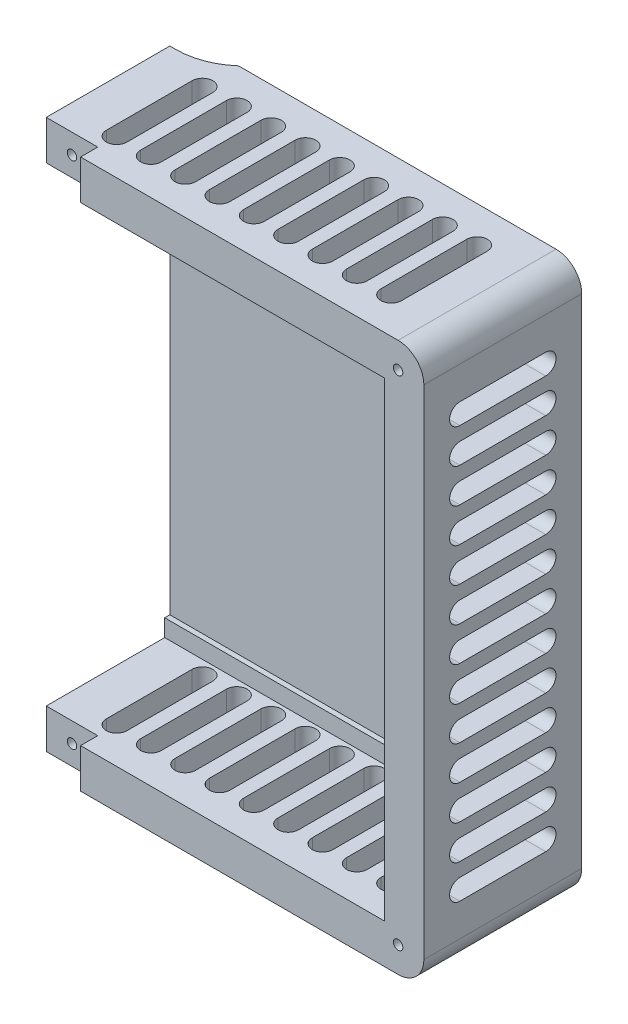
SolidWorks part; units mm, degrees
ref_plane "Front Plane" through (0, 0, 0) normal (0, 0, 1) x (1, 0, 0)
ref_plane "Top Plane" through (0, 0, 0) normal (0, 1, 0) x (1, 0, 0)
ref_plane "Right Plane" through (0, 0, 0) normal (1, 0, 0) x (0, 0, -1)
sketch "Sketch1" plane through (0, 0, 0) normal (0, 0, 1) x (1, 0, 0)
  line L1 (-115, 80) -> (115, 80)
  line L2 (-115, 80) -> (-115, -80)
  line L3 (-115, -80) -> (115, -80)
  line L4 (115, 80) -> (115, -80)
  line L5 (-115, 80) -> (115, -80) construction
  line L6 (-115, -80) -> (115, 80) construction
  point P0 (0, 0)
  dimension "D1" = 230
  dimension "D2" = 160
extrude "Boss-Extrude1" add sketch "Sketch1" along normal blind 46
shell "Shell1" thickness 11.5 removed face at (0, 0, 46)
sketch "Sketch3" plane through (0, 0, 46) normal (0, 0, 1) x (1, 0, 0)
  line L1 (-115, -80) -> (115, -80) construction
  line L2 (0, 80) -> (-115, 80)
  line L3 (0, 80) -> (0, -80)
  line L4 (0, -80) -> (-115, -80)
  line L5 (-115, 80) -> (-115, -80)
  line L7 (-115, 80) -> (-115, -80) construction
  dimension "D1" = 115
extrude "Cut-Extrude3" cut sketch "Sketch3" against normal up to surface (46 mm away) up to face at (0, 0, 0)
ref_plane "Plane1" through (0, 0, 23) normal (0, 0, 1) x (1, 0, 0)
sketch "Sketch12" plane through (0, 0, 11.5) normal (0, 0, 1) x (1, 0, 0)
  line L0 (103.5, 68.5) -> (0, 68.5) construction
  line L1 (103.5, 68.5) -> (0, 68.5)
  line L2 (103.5, 68.5) -> (103.5, -68.5)
  line L3 (103.5, -68.5) -> (0, -68.5)
  line L4 (0, 68.5) -> (0, -68.5)
  line L5 (103.5, 68.5) -> (0, -68.5) construction
  line L6 (103.5, -68.5) -> (0, 68.5) construction
  line L7 (103.5, -68.5) -> (103.5, 68.5) construction
  line L8 (0, -68.5) -> (103.5, -68.5) construction
  line L9 (0, -68.5) -> (0, 68.5) construction
  point P0 (51.75, 0)
extrude "Cut-Extrude11" cut sketch "Sketch12" against normal blind 5
sketch "Sketch13" plane through (0, 0, 6.5) normal (0, 0, 1) x (1, 0, 0)
  line L0 (103.5, -68.5) -> (103.5, 68.5) construction
  line L1 (91, 63.5) -> (0, 63.5)
  line L2 (98.5, 56) -> (98.5, -56)
  line L3 (91, -63.5) -> (0, -63.5)
  line L4 (0, 63.5) -> (0, -63.5)
  line L5 (98.5, 63.5) -> (0, -63.5) construction
  line L6 (98.5, -63.5) -> (0, 63.5) construction
  line L7 (103.5, 68.5) -> (0, 68.5) construction
  line L9 (0, -68.5) -> (103.5, -68.5) construction
  arc A0 (98.5, -56) -> (91, -63.5) centre (91, -56) cw
  arc A1 (91, 63.5) -> (98.5, 56) centre (91, 56) cw
  point P0 (49.25, 0)
  dimension "D3" = 7.5
  dimension "D1" = 5
  dimension "D2" = 5
  dimension "D4" = 5
extrude "Cut-Extrude12" cut sketch "Sketch13" against normal blind 1.5
sketch "Sketch14" plane through (0, 80, 0) normal (0, 1, 0) x (1, 0, 0)
  line L0 (98, -35.5) -> (98, -10.5)
  line L1 (92, -35.5) -> (92, -10.5)
  line L3 (115, -46) -> (115, 0) construction
  line L4 (115, -46) -> (0, -46) construction
  line L6 (88, -35.5) -> (88, -10.5)
  line L7 (82, -35.5) -> (82, -10.5)
  line L8 (78, -35.5) -> (78, -10.5)
  line L9 (72, -35.5) -> (72, -10.5)
  line L10 (68, -35.5) -> (68, -10.5)
  line L11 (62, -35.5) -> (62, -10.5)
  line L12 (58, -35.5) -> (58, -10.5)
  line L13 (52, -35.5) -> (52, -10.5)
  line L14 (48, -35.5) -> (48, -10.5)
  line L15 (42, -35.5) -> (42, -10.5)
  line L16 (38, -35.5) -> (38, -10.5)
  line L17 (32, -35.5) -> (32, -10.5)
  line L18 (28, -35.5) -> (28, -10.5)
  line L19 (22, -35.5) -> (22, -10.5)
  line L20 (18, -35.5) -> (18, -10.5)
  line L21 (12, -35.5) -> (12, -10.5)
  arc A0 (98, -35.5) -> (92, -35.5) centre (95, -35.5) cw
  arc A1 (92, -10.5) -> (98, -10.5) centre (95, -10.5) cw
  arc A2 (88, -35.5) -> (82, -35.5) centre (85, -35.5) cw
  arc A3 (82, -10.5) -> (88, -10.5) centre (85, -10.5) cw
  arc A4 (78, -35.5) -> (72, -35.5) centre (75, -35.5) cw
  arc A5 (72, -10.5) -> (78, -10.5) centre (75, -10.5) cw
  arc A6 (68, -35.5) -> (62, -35.5) centre (65, -35.5) cw
  arc A7 (62, -10.5) -> (68, -10.5) centre (65, -10.5) cw
  arc A8 (58, -35.5) -> (52, -35.5) centre (55, -35.5) cw
  arc A9 (52, -10.5) -> (58, -10.5) centre (55, -10.5) cw
  arc A10 (48, -35.5) -> (42, -35.5) centre (45, -35.5) cw
  arc A11 (42, -10.5) -> (48, -10.5) centre (45, -10.5) cw
  arc A12 (38, -35.5) -> (32, -35.5) centre (35, -35.5) cw
  arc A13 (32, -10.5) -> (38, -10.5) centre (35, -10.5) cw
  arc A14 (28, -35.5) -> (22, -35.5) centre (25, -35.5) cw
  arc A15 (22, -10.5) -> (28, -10.5) centre (25, -10.5) cw
  arc A16 (18, -35.5) -> (12, -35.5) centre (15, -35.5) cw
  arc A17 (12, -10.5) -> (18, -10.5) centre (15, -10.5) cw
  point P8 (95, -38.5)
  dimension "D2" = 3
  dimension "D3" = 17
  dimension "D1" = 25
  dimension "D4" = 7.5
  dimension "D5" = 9
extrude "Cut-Extrude13" cut sketch "Sketch14" against normal blind 12
mirror "Mirror9" about plane through (0, 0, 0) normal (0, 1, 0) of "Cut-Extrude13"
sketch "Sketch15" plane through (115, 0, 0) normal (1, 0, 0) x (0, 0, -1)
  line L0 (-35.5, -63) -> (-10.5, -63)
  line L1 (-10.5, -57) -> (-35.5, -57)
  line L2 (-46, -80) -> (0, -80) construction
  line L3 (-46, -80) -> (-46, 80) construction
  line L9 (-35.5, -53) -> (-10.5, -53)
  line L10 (-10.5, -47) -> (-35.5, -47)
  line L11 (-35.5, -43) -> (-10.5, -43)
  line L12 (-10.5, -37) -> (-35.5, -37)
  line L13 (-35.5, -33) -> (-10.5, -33)
  line L14 (-10.5, -27) -> (-35.5, -27)
  line L15 (-35.5, -23) -> (-10.5, -23)
  line L16 (-10.5, -17) -> (-35.5, -17)
  line L17 (-35.5, -13) -> (-10.5, -13)
  line L18 (-10.5, -7) -> (-35.5, -7)
  line L19 (-35.5, -3) -> (-10.5, -3)
  line L20 (-10.5, 3) -> (-35.5, 3)
  line L21 (-35.5, 7) -> (-10.5, 7)
  line L22 (-10.5, 13) -> (-35.5, 13)
  line L23 (-35.5, 17) -> (-10.5, 17)
  line L24 (-10.5, 23) -> (-35.5, 23)
  line L25 (-35.5, 27) -> (-10.5, 27)
  line L26 (-10.5, 33) -> (-35.5, 33)
  line L27 (-35.5, 37) -> (-10.5, 37)
  line L28 (-10.5, 43) -> (-35.5, 43)
  line L29 (-35.5, 47) -> (-10.5, 47)
  line L30 (-10.5, 53) -> (-35.5, 53)
  line L31 (-35.5, 57) -> (-10.5, 57)
  line L32 (-10.5, 63) -> (-35.5, 63)
  arc A0 (-10.5, -63) -> (-10.5, -57) centre (-10.5, -60) ccw
  arc A1 (-35.5, -57) -> (-35.5, -63) centre (-35.5, -60) ccw
  arc A2 (-35.5, -47) -> (-35.5, -53) centre (-35.5, -50) ccw
  arc A3 (-10.5, -53) -> (-10.5, -47) centre (-10.5, -50) ccw
  arc A4 (-35.5, -37) -> (-35.5, -43) centre (-35.5, -40) ccw
  arc A5 (-10.5, -43) -> (-10.5, -37) centre (-10.5, -40) ccw
  arc A6 (-35.5, -27) -> (-35.5, -33) centre (-35.5, -30) ccw
  arc A7 (-10.5, -33) -> (-10.5, -27) centre (-10.5, -30) ccw
  arc A8 (-35.5, -17) -> (-35.5, -23) centre (-35.5, -20) ccw
  arc A9 (-10.5, -23) -> (-10.5, -17) centre (-10.5, -20) ccw
  arc A10 (-35.5, -7) -> (-35.5, -13) centre (-35.5, -10) ccw
  arc A11 (-10.5, -13) -> (-10.5, -7) centre (-10.5, -10) ccw
  arc A12 (-35.5, 3) -> (-35.5, -3) centre (-35.5, 0) ccw
  arc A13 (-10.5, -3) -> (-10.5, 3) centre (-10.5, 0) ccw
  arc A14 (-35.5, 13) -> (-35.5, 7) centre (-35.5, 10) ccw
  arc A15 (-10.5, 7) -> (-10.5, 13) centre (-10.5, 10) ccw
  arc A16 (-35.5, 23) -> (-35.5, 17) centre (-35.5, 20) ccw
  arc A17 (-10.5, 17) -> (-10.5, 23) centre (-10.5, 20) ccw
  arc A18 (-35.5, 33) -> (-35.5, 27) centre (-35.5, 30) ccw
  arc A19 (-10.5, 27) -> (-10.5, 33) centre (-10.5, 30) ccw
  arc A20 (-35.5, 43) -> (-35.5, 37) centre (-35.5, 40) ccw
  arc A21 (-10.5, 37) -> (-10.5, 43) centre (-10.5, 40) ccw
  arc A22 (-35.5, 53) -> (-35.5, 47) centre (-35.5, 50) ccw
  arc A23 (-10.5, 47) -> (-10.5, 53) centre (-10.5, 50) ccw
  arc A24 (-35.5, 63) -> (-35.5, 57) centre (-35.5, 60) ccw
  arc A25 (-10.5, 57) -> (-10.5, 63) centre (-10.5, 60) ccw
  point P8 (-38.5, -60)
  dimension "D4" = 3
  dimension "D1" = 17
  dimension "D2" = 25
  dimension "D3" = 7.5
  dimension "D5" = 13
extrude "Cut-Extrude14" cut sketch "Sketch15" against normal blind 12
fillet "Fillet1" radius 7.5 2 edges at (115, -80, 23) (115, 80, 23)
sketch "Sketch16" plane through (0, 0, 46) normal (0, 0, 1) x (1, 0, 0)
  line L0 (107.5, 80) -> (0, 80) construction
  line L1 (115, -72.5) -> (115, 72.5) construction
  line L2 (0, -80) -> (107.5, -80) construction
  circle A0 centre (107.5, -72.5) radius 1.375
  circle A1 centre (107.5, 72.5) radius 1.375
  dimension "D1" = 2.75
  dimension "D4" = 2.75
  dimension "D2" = 7.5
  dimension "D3" = 7.5
  dimension "D5" = 7.5
  dimension "D6" = 7.5
extrude "Cut-Extrude15" cut sketch "Sketch16" against normal blind 10
sketch "Sketch17" plane through (0, 0, 46) normal (0, 0, 1) x (1, 0, 0)
  line L0 (0, 68.5) -> (0, 80) construction
  line L1 (15, 68.5) -> (-15, 68.5)
  line L2 (15, 68.5) -> (15, 80)
  line L3 (15, 80) -> (-15, 80)
  line L4 (-15, 68.5) -> (-15, 80)
  line L5 (15, 68.5) -> (-15, 80) construction
  line L6 (15, 80) -> (-15, 68.5) construction
  line L7 (103.5, 68.5) -> (0, 68.5) construction
  line L8 (107.5, 80) -> (0, 80) construction
  point P0 (0, 74.25)
  dimension "D1" = 30
extrude "Cut-Extrude16" cut sketch "Sketch17" against normal blind 5
sketch "Sketch18" plane through (0, 0, 41) normal (0, 0, 1) x (1, 0, 0)
  line L0 (0, 68.5) -> (15, 68.5) construction
  line L1 (0, 80) -> (0, 68.5) construction
  circle A0 centre (7.5, 74.25) radius 1.375
  point P6 (0, 74.25)
  dimension "D1" = 2.75
  dimension "D2" = 5.75
  dimension "D3" = 7.5
extrude "Cut-Extrude17" cut sketch "Sketch18" against normal blind 8
mirror "Mirror10" about plane through (0, 0, 0) normal (0, 1, 0) of "Cut-Extrude16", "Cut-Extrude17"
sketch "Sketch19" plane through (0, 0, 0) normal (0, 0, -1) x (-1, 0, 0)
  line L0 (0, 80) -> (0, -80) construction
  line L1 (-15, -68.5) -> (15, -68.5)
  line L2 (-15, -68.5) -> (-15, -80)
  line L3 (-15, -80) -> (15, -80)
  line L4 (15, -68.5) -> (15, -80)
  line L5 (-15, -68.5) -> (15, -80) construction
  line L6 (-15, -80) -> (15, -68.5) construction
  line L7 (0, -80) -> (-107.5, -80) construction
  point P0 (0, -74.25)
  dimension "D1" = 11.5
  dimension "D2" = 30
extrude "Cut-Extrude18" cut sketch "Sketch19" against normal blind 5
sketch "Sketch20" plane through (0, 0, 5) normal (0, 0, -1) x (-1, 0, 0)
  line L0 (0, -80) -> (0, -68.5) construction
  line L1 (-15, -80) -> (0, -80) construction
  circle A0 centre (-7.5, -74.25) radius 1.375
  dimension "D1" = 2.75
  dimension "D2" = 7.5
  dimension "D3" = 5.75
extrude "Cut-Extrude19" cut sketch "Sketch20" against normal blind 8
mirror "Mirror11" about plane through (0, 0, 0) normal (0, 1, 0) of "Cut-Extrude19", "Cut-Extrude18"
fillet "Fillet2" radius 20 1 edges at (15, 74.25, 5)
fillet "Fillet3" radius 20 1 edges at (15, -74.25, 5)
